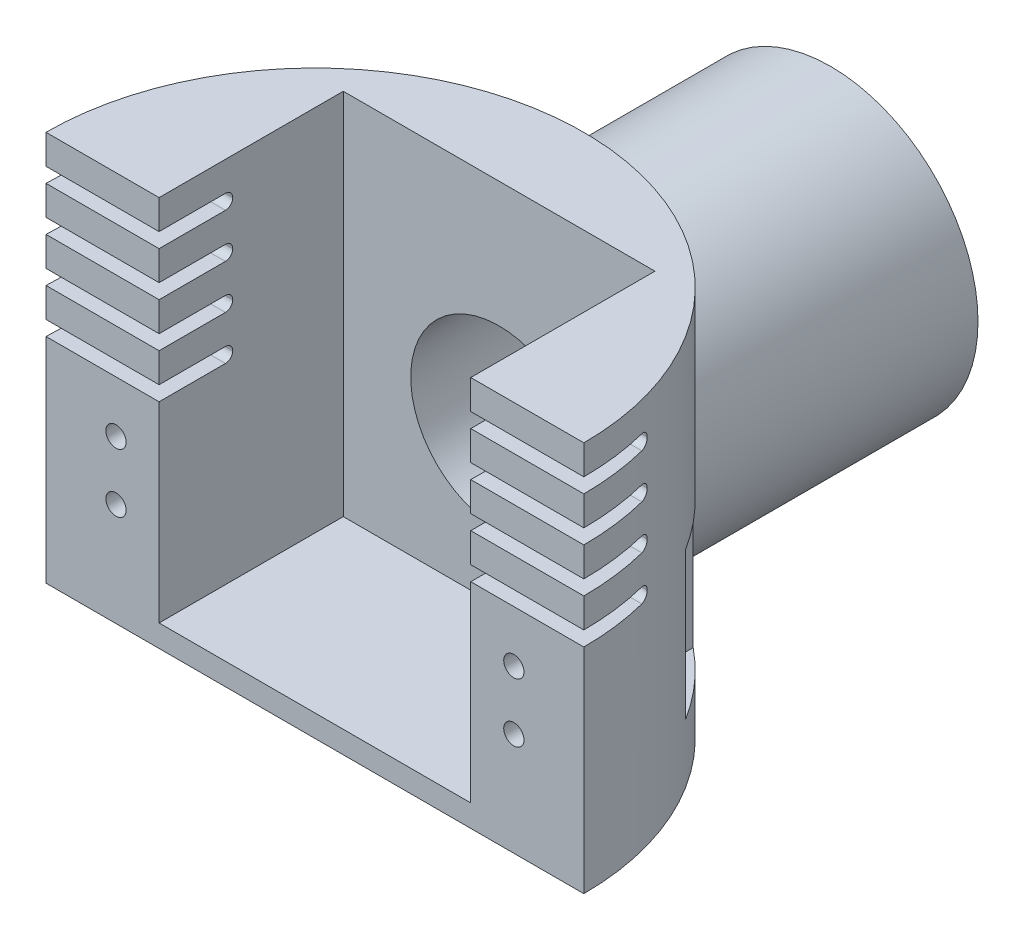
SolidWorks part; units mm, degrees
ref_plane "Front Plane" through (0, 0, 0) normal (0, 0, 1) x (1, 0, 0)
ref_plane "Top Plane" through (0, 0, 0) normal (0, 1, 0) x (1, 0, 0)
ref_plane "Right Plane" through (0, 0, 0) normal (1, 0, 0) x (0, 0, -1)
sketch "Sketch1" plane through (0, 0, 0) normal (0, 1, 0) x (1, 0, 0)
  circle A0 centre (0, 0) radius 36.5
  dimension "D1" = 73
extrude "Boss-Extrude1" add sketch "Sketch1" along normal blind 3
sketch "Sketch2" plane through (0, 3, 0) normal (0, 1, 0) x (1, 0, 0)
  line L0 (-11, 0) -> (-11, -34.803)
  line L1 (11, 0) -> (11, -34.803)
  arc A0 (11, -34.803) -> (-11, -34.803) centre (0, 0) ccw
  arc A1 (11, 0) -> (-11, 0) centre (0, 0) ccw
  dimension "D1" = 73
  dimension "D2" = 11
extrude "Boss-Extrude2" add sketch "Sketch2" along normal blind 7
sketch "Sketch3" plane through (0, 3, 0) normal (0, 1, 0) x (1, 0, 0)
  circle A0 centre (0, 0) radius 4.15
  dimension "D1" = 8.3
extrude "Cut-Extrude1" cut sketch "Sketch3" against normal up to next
sketch "Sketch4" plane through (0, 10, 0) normal (0, 1, 0) x (1, 0, 0)
  line L1 (-6.35, -3.6662) -> (-6.35, -35.9434)
  line L3 (6.35, -3.6662) -> (6.35, 3.6662)
  line L4 (6.35, 3.6662) -> (0, 7.3323)
  line L5 (0, 7.3323) -> (-6.35, 3.6662)
  line L6 (-6.35, 3.6662) -> (-6.35, -3.6662)
  line L8 (6.35, -3.6662) -> (6.35, -35.9434)
  line L10 (-3.175, -5.4993) -> (-0.7775, -6.8834) [skipped]
  line L11 (3.175, -5.4993) -> (6.35, -3.6662) [skipped]
  arc A0 (6.35, -35.9434) -> (-6.35, -35.9434) centre (0, 0) ccw
  arc A1 (6.35, 0) -> (-6.35, 0) centre (0, 0) ccw construction
  arc A2 (6.35, -35.9434) -> (-6.35, -35.9434) centre (0, 0) ccw
  arc M3 (-11, 0) -> (11, 0) centre (0, 0) cw
  line M4 (11, 0) -> (11, -34.803)
  arc M5 (11, -34.803) -> (-11, -34.803) centre (0, 0) ccw
  line M6 (-11, -34.803) -> (-11, 0)
  dimension "D1" = 73
  dimension "D2" = 6.35
extrude "Boss-Extrude3" add sketch "Sketch4" along normal blind 8 contours M6 M3 M4 M5 | L8 A0 L1 L6 L5 L4 L3 M4 M3 M6 region at (-6.8684, 10, 19.8048) region at (0, 10, -35.4796)
sketch "Sketch5" plane through (0, 18, 0) normal (0, 1, 0) x (1, 0, 0)
  line L5 (0, 0) -> (24, 21.15) construction
  circle A0 centre (0, 0) radius 36.5
  dimension "D1" = 73
extrude "Boss-Extrude4" add sketch "Sketch5" along normal blind 5
sketch "Sketch6" plane through (0, 23, 0) normal (0, 1, 0) x (1, 0, 0)
  line L1 (-21.15, -25) -> (21.15, -25)
  line L2 (-21.15, -25) -> (-21.15, 25)
  line L3 (-21.15, 25) -> (21.15, 25)
  line L4 (21.15, -25) -> (21.15, 25)
  line L5 (-21.15, -25) -> (21.15, 25) construction
  line L6 (-21.15, 25) -> (21.15, -25) construction
  circle A0 centre (0, 0) radius 36.5
  dimension "D1" = 73
  dimension "D2" = 42.3
  dimension "D3" = 50
extrude "Boss-Extrude5" add sketch "Sketch6" along normal blind 50
ref_plane "Plane1" through (0, 0, 36.5) normal (0, 0, -1) x (-1, 0, 0)
sketch "Sketch7" plane through (0, 0, 36.5) normal (0, 0, -1) x (-1, 0, 0)
  line L0 (-36.5, 0) -> (36.5, 0) construction
  line L1 (-15.1333, 2.0001) -> (14.8667, 2.0001)
  line L3 (-15.0444, 21.9999) -> (14.9556, 21.9999)
  line L6 (-5.6045, 15.7698) -> (5.6045, 8.2302) construction
  line L7 (0, 12) -> (5.6933, 15.7697) construction
  arc A0 (-15.0444, 21.9999) -> (-15.1333, 2.0001) centre (-15.0444, 11.9998) ccw
  arc A1 (14.8667, 2.0001) -> (14.9556, 21.9999) centre (14.9556, 11.9998) ccw
  point P0 (0, 12)
  dimension "D1" = 12
  dimension "D2" = 20
  dimension "D3" = 30
  dimension "D4" = 30
extrude "Cut-Extrude3" cut sketch "Sketch7" along normal blind 12
ref_plane "Plane2" through (0, 0, -70) normal (0, 0, 1) x (1, 0, 0)
sketch "Sketch10" plane through (0, 0, -70) normal (0, 0, 1) x (1, 0, 0)
  line L0 (-36.5, 0) -> (36.5, 0) construction
  circle A0 centre (0, 44) radius 20
  dimension "D1" = 40
  dimension "D2" = 44
extrude "Boss-Extrude6" add sketch "Sketch10" along normal up to next
sketch "Sketch8" plane through (0, 73, 0) normal (0, 1, 0) x (1, 0, 0)
  line L1 (-36.5, 0) -> (36.5, 0)
  line L2 (-36.5, 0) -> (-36.5, -36.5)
  line L3 (-36.5, -36.5) -> (36.5, -36.5)
  line L4 (36.5, 0) -> (36.5, -36.5)
  circle A0 centre (0, 0) radius 36.5 construction
  dimension "D1" = 73
  dimension "D2" = 36.5
extrude "Cut-Extrude4" cut sketch "Sketch8" against normal through all
sketch "Sketch9" plane through (0, 0, -25) normal (0, 0, 1) x (1, 0, 0)
  line L0 (21.15, 73) -> (21.15, 23) construction
  line L1 (21.15, 23) -> (-21.15, 23) construction
  circle A0 centre (0, 44) radius 4
  dimension "D1" = 21.15
  dimension "D2" = 8
  dimension "D3" = 21
extrude "Cut-Extrude5" cut sketch "Sketch9" against normal up to next
sketch "Sketch11" plane through (0, 0, -70) normal (0, 0, -1) x (-1, 0, 0)
  circle A0 centre (0, 44) radius 11
  dimension "D1" = 22
extrude "Cut-Extrude6" cut sketch "Sketch11" against normal blind 7
sketch "Sketch12" plane through (0, 0, -25) normal (0, 0, 1) x (1, 0, 0)
  circle A0 centre (0, 44) radius 12
  dimension "D1" = 24
extrude "Cut-Extrude7" cut sketch "Sketch12" against normal blind 35
ref_plane "Plane3" through (0, 0, -7.6) normal (0, 0, 1) x (1, 0, 0)
sketch "Sketch13" plane through (0, 0, -7.6) normal (0, 0, 1) x (1, 0, 0)
  line L0 (0, -38.5) -> (0, 38.5) construction
  line L1 (-23, 48) -> (-31, 48)
  line L2 (-23, 48) -> (-23, 28)
  line L3 (-23, 28) -> (-31, 28)
  line L4 (-31, 48) -> (-31, 28)
  line L5 (31, 48) -> (23, 48)
  line L6 (31, 48) -> (31, 28)
  line L7 (31, 28) -> (23, 28)
  line L8 (23, 48) -> (23, 28)
  line L9 (36.5, 73) -> (-36.5, 73) construction
  dimension "D1" = 8
  dimension "D2" = 8
  dimension "D3" = 23
  dimension "D4" = 23
  dimension "D5" = 25
  dimension "D6" = 25
  dimension "D7" = 20
  dimension "D8" = 20
extrude "Cut-Extrude9" cut sketch "Sketch13" against normal up to next
sketch "Sketch14" plane through (0, 0, -7.6) normal (0, 0, -1) x (-1, 0, 0)
  line L0 (23, 48) -> (31, 48) construction
  line L1 (-31, 48) -> (-23, 48) construction
  line L2 (23, 48) -> (23, 28) construction
  line L3 (-23, 28) -> (-23, 48) construction
  line L4 (-23, 48) -> (-23, 28) construction
  circle A0 centre (27, 42) radius 1.375
  circle A1 centre (27, 34) radius 1.375
  circle A2 centre (-27, 42) radius 1.375
  circle A3 centre (-27, 34) radius 1.375
  dimension "D1" = 2.75
  dimension "D2" = 2.75
  dimension "D3" = 2.75
  dimension "D4" = 2.75
  dimension "D5" = 6
  dimension "D6" = 6
  dimension "D7" = 8
  dimension "D8" = 8
  dimension "D9" = 4
  dimension "D10" = 4
  dimension "D11" = 4
  dimension "D12" = 4
extrude "Cut-Extrude10" cut sketch "Sketch14" against normal up to next
sketch "Sketch16" plane through (0, 0, -7.6) normal (0, 0, -1) x (-1, 0, 0)
  circle A0 centre (-27, 42) radius 2.65
  circle A1 centre (-27, 34) radius 2.65
  circle A2 centre (27, 42) radius 2.65
  circle A3 centre (27, 34) radius 2.65
  dimension "D1" = 5.3
  dimension "D2" = 5.3
  dimension "D3" = 5.3
  dimension "D4" = 5.3
extrude "Cut-Extrude14" cut sketch "Sketch16" against normal blind 2.6
ref_plane "Plane4" through (36.5, 0, 0) normal (1, 0, 0) x (0, 0, -1)
sketch "Sketch17" plane through (36.5, 0, 0) normal (1, 0, 0) x (0, 0, -1)
  line L0 (0, 0) -> (0, 73) construction
  line L1 (0, 69) -> (10, 69)
  line L2 (0, 69) -> (0, 67)
  line L3 (0, 67) -> (10, 67)
  line L4 (10, 69) -> (10, 67)
  line L6 (0, 63) -> (10, 63)
  line L7 (0, 63) -> (0, 61)
  line L8 (0, 61) -> (10, 61)
  line L9 (10, 63) -> (10, 61)
  line L10 (0, 57) -> (10, 57)
  line L11 (0, 57) -> (0, 55)
  line L12 (0, 55) -> (10, 55)
  line L13 (10, 57) -> (10, 55)
  line L14 (0, 51) -> (10, 51)
  line L15 (0, 51) -> (0, 49)
  line L16 (0, 49) -> (10, 49)
  line L17 (10, 51) -> (10, 49)
  dimension "D1" = 10
  dimension "D2" = 2
  dimension "D3" = 2
  dimension "D4" = 2
  dimension "D5" = 2
  dimension "D6" = 4
  dimension "D7" = 4
  dimension "D8" = 4
  dimension "D9" = 4
  dimension "D10" = 10
  dimension "D11" = 10
  dimension "D12" = 10
extrude "Cut-Extrude15" cut sketch "Sketch17" against normal through all
fillet "Fillet1" radius 1 16 edges at (-28.1267, 49, -10) (-28.1267, 55, -10) (-28.1267, 61, -10) (-28.1267, 67, -10) (28.1267, 67, -10) (28.1267, 61, -10) (28.1267, 55, -10) (28.1267, 49, -10) (28.1267, 51, -10) (28.1267, 57, -10) (28.1267, 63, -10) (28.1267, 69, -10) (-28.1267, 51, -10) (-28.1267, 57, -10) (-28.1267, 63, -10) (-28.1267, 69, -10)
sketch "Sketch19" plane through (0, 0, 0) normal (0, -1, 0) x (1, 0, 0)
  circle A0 centre (0, 0) radius 36.5
extrude "Cut-Extrude16" cut sketch "Sketch19" against normal blind 20
